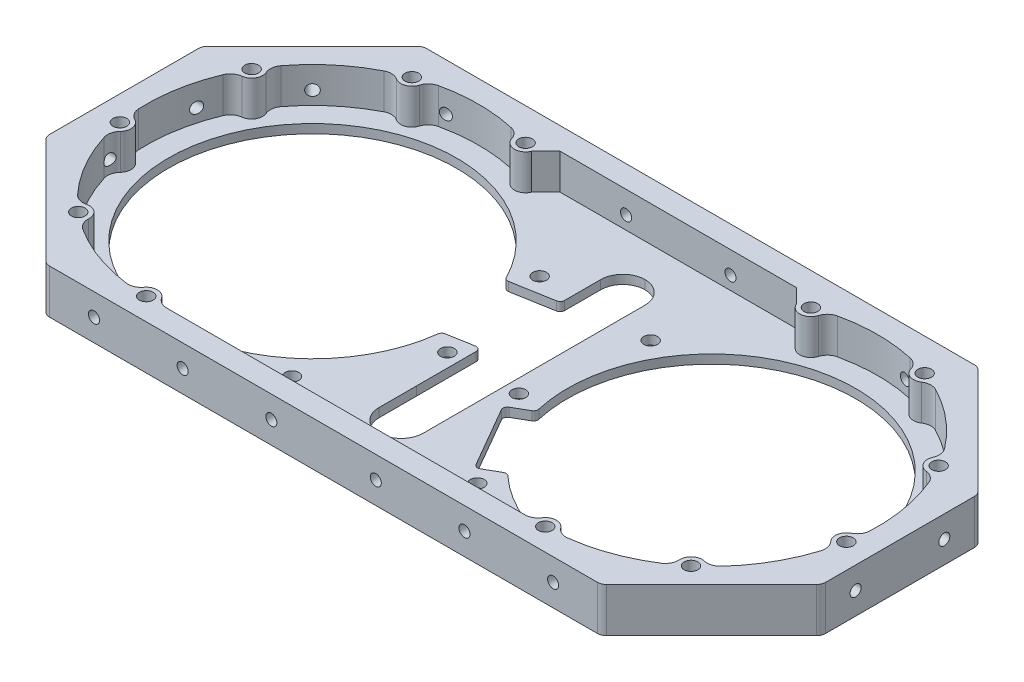
SolidWorks part; units mm, degrees
note: The reader was unsure of these and kept them because the rebuilt part matched: shared geometry of "草图2<8>".
ref_plane "前视基准面" through (0, 0, 0) normal (0, 0, 1) x (1, 0, 0)
ref_plane "上视基准面" through (0, 0, 0) normal (0, 1, 0) x (1, 0, 0)
ref_plane "右视基准面" through (0, 0, 0) normal (1, 0, 0) x (0, 0, -1)
sketch "草图2" plane through (0, 0, 0) normal (0, 1, 0) x (1, 0, 0)
  line L0 (0, 0) -> (90, 0) construction
  line L1 (16.5685, 40) -> (-16.5685, 40)
  line L2 (-16.5685, 40) -> (-40, 16.5685)
  line L3 (-40, 16.5685) -> (-40, -16.5685)
  line L4 (-40, -16.5685) -> (-16.5685, -40)
  line L5 (-16.5685, -40) -> (16.5685, -40)
  line L6 (16.5685, -40) -> (45, -11.5685)
  line L8 (45, 11.5685) -> (16.5685, 40)
  line L10 (16.5685, 40) -> (73.4315, 40)
  line L11 (130, 16.5685) -> (106.5685, 40)
  line L12 (106.5685, 40) -> (73.4315, 40)
  line L13 (73.4315, 40) -> (45, 11.5685)
  line L15 (45, -11.5685) -> (73.4315, -40)
  line L16 (73.4315, -40) -> (106.5685, -40)
  line L17 (106.5685, -40) -> (130, -16.5685)
  line L18 (130, -16.5685) -> (130, 16.5685)
  line L19 (40, -15.5147) -> (40, 0) [skipped]
  line L20 (50, -14.3614) -> (50, -29.8761) [skipped]
  line L21 (16.5685, -40) -> (73.4315, -40)
  line L22 (45, 11.5685) -> (45, -11.5685)
  line L23 (16.5685, 42.5) -> (-17.6041, 42.5)
  line L26 (57.524, 18.75) -> (57.2549, 17.2235)
  line L27 (53.0697, -6.5118) -> (53.8447, -7.8541)
  line L33 (58.7114, 19.7463) -> (57.524, 18.75)
  line L34 (53.3389, -4.9854) -> (53.0697, -6.5118)
  line L35 (-17.6041, 42.5) -> (-42.5, 17.6041)
  line L36 (-42.5, 17.6041) -> (-42.5, -17.6041)
  line L37 (-42.5, -17.6041) -> (-17.6041, -42.5)
  line L38 (-17.6041, -42.5) -> (16.5685, -42.5)
  line L39 (16.5685, -42.5) -> (73.4315, -42.5)
  line L40 (77.1742, 35.2385) -> (75.9869, 34.2422) [skipped]
  line L41 (102.8258, 35.2385) -> (101.2758, 35.2385) [skipped]
  line L42 (122.476, 18.75) -> (121.2886, 19.7463) [skipped]
  line L43 (126.9303, -6.5118) -> (126.6611, -4.9854) [skipped]
  line L44 (114.1045, -28.7267) -> (114.8795, -27.3843) [skipped]
  line L45 (90, -37.5) -> (91.4565, -36.9699) [skipped]
  line L46 (65.8955, -28.7267) -> (67.352, -29.2568) [skipped]
  line L47 (73.4315, -42.5) -> (107.6041, -42.5)
  line L48 (107.6041, -42.5) -> (132.5, -17.6041)
  line L49 (132.5, -17.6041) -> (132.5, 17.6041)
  line L50 (132.5, 17.6041) -> (107.6041, 42.5)
  line L51 (107.6041, 42.5) -> (73.4315, 42.5)
  line L52 (16.5685, 42.5) -> (73.4315, 42.5)
  line L53 (15.1452, 34.3056) -> (18.7041, 37.8645)
  line L56 (40, -37.5) -> (50, -37.5)
  line L59 (50, -30) -> (40, -30)
  line L60 (90, -37.5) -> (0, -37.5)
  line L61 (18.7041, 37.8645) -> (20.8396, 40)
  line L62 (50, -30) -> (50, 30)
  line L63 (74.8548, 34.3056) -> (71.2959, 37.8645)
  line L64 (71.2959, 37.8645) -> (69.1604, 40)
  line L65 (50, 30) -> (40, 30)
  line L66 (40, -30) -> (40, 30)
  line L67 (50, -30) -> (40, 30) construction
  line L68 (50, 30) -> (40, -30) construction
  circle A0 centre (0, 0) radius 40 construction
  circle A1 centre (0, 0) radius 37.5
  circle A2 centre (0, -37.5) radius 1.55
  circle A3 centre (-24.1045, -28.7267) radius 1.55
  circle A4 centre (-36.9303, -6.5118) radius 1.55
  circle A5 centre (-32.476, 18.75) radius 1.55
  circle A6 centre (-12.8258, 35.2385) radius 1.55
  circle A7 centre (12.8258, 35.2385) radius 1.55
  circle A8 centre (32.476, 18.75) radius 1.55
  circle A9 centre (36.9303, -6.5118) radius 1.55
  circle A10 centre (24.1045, -28.7267) radius 1.55
  circle A11 centre (90, 0) radius 40 construction
  circle A12 centre (90, 0) radius 37.5
  circle A13 centre (77.1742, 35.2385) radius 1.55
  circle A14 centre (102.8258, 35.2385) radius 1.55
  circle A15 centre (122.476, 18.75) radius 1.55
  circle A16 centre (126.9303, -6.5118) radius 1.55
  circle A17 centre (114.1045, -28.7267) radius 1.55
  circle A18 centre (90, -37.5) radius 1.55
  circle A19 centre (65.8955, -28.7267) radius 1.55
  circle A20 centre (53.0697, -6.5118) radius 1.55
  circle A21 centre (57.524, 18.75) radius 1.55
  circle A22 centre (0, 0) radius 32.5
  circle A23 centre (90, 0) radius 32.5
  circle A24 centre (0, -37.5) radius 2.5
  circle A25 centre (24.1045, -28.7267) radius 2.5
  circle A26 centre (36.9303, -6.5118) radius 2.5
  circle A27 centre (-24.1045, -28.7267) radius 2.5
  circle A28 centre (-36.9303, -6.5118) radius 2.5
  circle A29 centre (-32.476, 18.75) radius 2.5
  circle A30 centre (-12.8258, 35.2385) radius 2.5
  circle A31 centre (12.8258, 35.2385) radius 2.5
  circle A32 centre (32.476, 18.75) radius 2.5
  circle A33 centre (90, -37.5) radius 2.5
  circle A34 centre (65.8955, -28.7267) radius 2.5
  circle A35 centre (53.0697, -6.5118) radius 2.5
  circle A36 centre (57.524, 18.75) radius 2.5
  circle A37 centre (77.1742, 35.2385) radius 2.5
  circle A38 centre (102.8258, 35.2385) radius 2.5
  circle A39 centre (122.476, 18.75) radius 2.5
  circle A40 centre (126.9303, -6.5118) radius 2.5
  circle A41 centre (114.1045, -28.7267) radius 2.5
  point P13 (0, -37.5)
  point P35 (0, 0)
  point P73 (90, 0)
  point P84 (45, 0)
  point P86 (45, 0)
  point P140 (90, 0)
  dimension "D1" = 80
  dimension "D2" = 75
  dimension "D3" = 3.1
  dimension "D6" = 80
  dimension "D7" = 75
  dimension "D8" = 3.1
  dimension "D11" = 65
  dimension "D12" = 65
  dimension "D16" = 5
  dimension "D5" = 90
  dimension "D10" = 2.5
  dimension "D13" = 10
  dimension "D14" = 60
  dimension "D15" = 0.95
  dimension "D4" = 9
  dimension "D9" = 9
  dimension "D17" = 9
extrude "凸台-拉伸3" add sketch "草图2" along normal blind 10
extrude "凸台-拉伸4" add sketch "草图2<8>" along normal blind 2
sketch "草图2<8>" plane through (0, 0, 0) normal (0, 1, 0) x (1, 0, 0) same geometry as "草图2"
sketch "草图3" plane through (0, 2, 0) normal (0, 1, 0) x (1, 0, 0)
  line L0 (34.0024, 19.0192) -> (38.4567, -6.2427)
  line L1 (34.697, 15.0799) -> (37.7622, -2.3034)
  line L2 (34.697, 15.0799) -> (26.8185, 13.6907)
  line L3 (37.7622, -2.3034) -> (29.8837, -3.6926)
  line L4 (26.8185, 13.6907) -> (29.8837, -3.6926)
  line L5 (51.7274, -7.2868) -> (64.5531, -29.5017)
  line L6 (53.7274, -10.7509) -> (62.5531, -26.0376)
  line L7 (53.7274, -10.7509) -> (60.6556, -6.7509)
  line L8 (62.5531, -26.0376) -> (69.4813, -22.0376)
  line L9 (60.6556, -6.7509) -> (69.4813, -22.0376)
  line L10 (34.697, 15.0799) -> (37.7622, -2.3034)
  line L11 (34.697, 15.0799) -> (42.5755, 16.4691)
  line L12 (37.7622, -2.3034) -> (45.6406, -0.9142)
  line L13 (42.5755, 16.4691) -> (45.6406, -0.9142)
  circle A0 centre (36.9303, -6.5118) radius 1.55 construction
  circle A1 centre (32.476, 18.75) radius 1.55 construction
  circle A2 centre (36.9303, -6.5118) radius 1.55
  circle A3 centre (32.476, 18.75) radius 1.55
  circle A4 centre (65.8955, -28.7267) radius 1.55 construction
  circle A5 centre (53.0697, -6.5118) radius 1.55 construction
  circle A6 centre (65.8955, -28.7267) radius 1.55
  circle A7 centre (53.0697, -6.5118) radius 1.55
  line M99 (40, -16.5685) -> (40, 30)
  dimension "D4" = 4
  dimension "D1" = 4
  dimension "D2" = 4
  dimension "D3" = 8
  dimension "D5" = 4
  dimension "D6" = 8
  dimension "D7" = 8
extrude "切除-拉伸1" cut sketch "草图3" against normal blind 12 contours L2 L4 L3 L0 | L9 L7 L5 L8 | L0 L12 L11 M99 | L13 L11 L12 M99
fillet "圆角4" radius 1 8 edges at (67.3247, 1, 23.2827) (58.499, 1, 7.996) (62.5531, 1, 26.0376) (53.7274, 1, 10.7509) (32.3361, 1, 3.2602) (29.2709, 1, -14.1232) (40, 1, 1.9088) (40, 1, -16.015)
sketch "草图4" plane through (0, 2, 0) normal (0, 1, 0) x (1, 0, 0)
  line L0 (0, 37.5) -> (90, 37.5)
  line L5 (2.5, -37.5) -> (87.5, -37.5)
  line L6 (2.5, -37.5) -> (87.5, -37.5)
  line L9 (74.8548, 34.3056) -> (69.1604, 40)
  line L10 (69.1604, 40) -> (20.8396, 40)
  line L11 (20.8396, 40) -> (15.1452, 34.3056)
  line L17 (74.8548, 34.3056) -> (69.1604, 40)
  line L18 (69.1604, 40) -> (20.8396, 40)
  line L19 (20.8396, 40) -> (15.1452, 34.3056)
  arc A27 (92.4986, -37.4167) -> (87.5, -37.5) centre (90, -37.5) ccw
  arc A28 (92.4986, -37.4167) -> (112.1369, -30.2689) centre (90, 0) ccw
  arc A29 (115.965, -27.0568) -> (112.1369, -30.2689) centre (114.1045, -28.7267) ccw
  arc A30 (115.965, -27.0568) -> (126.4143, -8.958) centre (90, 0) ccw
  arc A31 (127.2821, -4.0367) -> (126.4143, -8.958) centre (126.9303, -6.5118) ccw
  arc A32 (127.2821, -4.0367) -> (123.6531, 16.5445) centre (90, 0) ccw
  arc A33 (121.1545, 20.8722) -> (123.6531, 16.5445) centre (122.476, 18.75) ccw
  arc A34 (121.1545, 20.8722) -> (105.1452, 34.3056) centre (90, 0) ccw
  arc A35 (100.4493, 36.0147) -> (105.1452, 34.3056) centre (102.8258, 35.2385) ccw
  arc A36 (100.4493, 36.0147) -> (79.5507, 36.0147) centre (90, 0) ccw
  arc A37 (74.8548, 34.3056) -> (79.5507, 36.0147) centre (77.1742, 35.2385) ccw
  arc A38 (10.4493, 36.0147) -> (15.1452, 34.3056) centre (12.8258, 35.2385) ccw
  arc A39 (10.4493, 36.0147) -> (-10.4493, 36.0147) centre (0, 0) ccw
  arc A40 (-15.1452, 34.3056) -> (-10.4493, 36.0147) centre (-12.8258, 35.2385) ccw
  arc A41 (-15.1452, 34.3056) -> (-31.1545, 20.8722) centre (0, 0) ccw
  arc A42 (-33.6531, 16.5445) -> (-31.1545, 20.8722) centre (-32.476, 18.75) ccw
  arc A43 (-33.6531, 16.5445) -> (-37.2821, -4.0367) centre (0, 0) ccw
  arc A44 (-36.4143, -8.958) -> (-37.2821, -4.0367) centre (-36.9303, -6.5118) ccw
  arc A45 (-36.4143, -8.958) -> (-25.965, -27.0568) centre (0, 0) ccw
  arc A46 (-22.1369, -30.2689) -> (-25.965, -27.0568) centre (-24.1045, -28.7267) ccw
  arc A47 (-22.1369, -30.2689) -> (-2.4986, -37.4167) centre (0, 0) ccw
  arc A48 (2.5, -37.5) -> (-2.4986, -37.4167) centre (0, -37.5) ccw
  arc A53 (92.4986, -37.4167) -> (87.5, -37.5) centre (90, -37.5) ccw
  arc A54 (92.4986, -37.4167) -> (112.1369, -30.2689) centre (90, 0) ccw
  arc A55 (115.965, -27.0568) -> (112.1369, -30.2689) centre (114.1045, -28.7267) ccw
  arc A56 (115.965, -27.0568) -> (126.4143, -8.958) centre (90, 0) ccw
  arc A57 (127.2821, -4.0367) -> (126.4143, -8.958) centre (126.9303, -6.5118) ccw
  arc A58 (127.2821, -4.0367) -> (123.6531, 16.5445) centre (90, 0) ccw
  arc A59 (121.1545, 20.8722) -> (123.6531, 16.5445) centre (122.476, 18.75) ccw
  arc A60 (121.1545, 20.8722) -> (105.1452, 34.3056) centre (90, 0) ccw
  arc A61 (100.4493, 36.0147) -> (105.1452, 34.3056) centre (102.8258, 35.2385) ccw
  arc A62 (100.4493, 36.0147) -> (79.5507, 36.0147) centre (90, 0) ccw
  arc A63 (74.8548, 34.3056) -> (79.5507, 36.0147) centre (77.1742, 35.2385) ccw
  arc A64 (10.4493, 36.0147) -> (15.1452, 34.3056) centre (12.8258, 35.2385) ccw
  arc A65 (10.4493, 36.0147) -> (-10.4493, 36.0147) centre (0, 0) ccw
  arc A66 (-15.1452, 34.3056) -> (-10.4493, 36.0147) centre (-12.8258, 35.2385) ccw
  arc A67 (-15.1452, 34.3056) -> (-31.1545, 20.8722) centre (0, 0) ccw
  arc A68 (-33.6531, 16.5445) -> (-31.1545, 20.8722) centre (-32.476, 18.75) ccw
  arc A69 (-33.6531, 16.5445) -> (-37.2821, -4.0367) centre (0, 0) ccw
  arc A70 (-36.4143, -8.958) -> (-37.2821, -4.0367) centre (-36.9303, -6.5118) ccw
  arc A71 (-36.4143, -8.958) -> (-25.965, -27.0568) centre (0, 0) ccw
  arc A72 (-22.1369, -30.2689) -> (-25.965, -27.0568) centre (-24.1045, -28.7267) ccw
  arc A73 (-22.1369, -30.2689) -> (-2.4986, -37.4167) centre (0, 0) ccw
  arc A74 (2.5, -37.5) -> (-2.4986, -37.4167) centre (0, -37.5) ccw
  dimension "D1" = 0
extrude "凸台-拉伸5" add sketch "草图4" along normal blind 8 contours L18 L19 L0 L17
fillet "圆角5" radius 3 21 edges at (-2.4986, 6, 37.4167) (-22.1369, 6, 30.2689) (-25.965, 6, 27.0568) (-36.4143, 6, 8.958) (-37.2821, 6, 4.0367) (-33.6531, 6, -16.5445) (-31.1545, 6, -20.8722) (-15.1452, 6, -34.3056) (-10.4493, 6, -36.0147) (10.4493, 6, -36.0147) (92.4986, 6, 37.4167) (115.965, 6, 27.0568) (112.1369, 6, 30.2689) (127.2821, 6, 4.0367) (126.4143, 6, 8.958) (121.1545, 6, -20.8722) (123.6531, 6, -16.5445) (100.4493, 6, -36.0147) (105.1452, 6, -34.3056) (79.5507, 6, -36.0147) (2.5, 6, 37.5)
fillet "圆角6" radius 3 1 edges at (87.5, 6, 37.5)
fillet "圆角7" radius 2 8 edges at (107.6041, 5, -42.5) (132.5, 5, -17.6041) (132.5, 5, 17.6041) (107.6041, 5, 42.5) (-17.6041, 5, 42.5) (-42.5, 5, 17.6041) (-42.5, 5, -17.6041) (-17.6041, 5, -42.5)
sketch "草图5" plane through (0, 0, -42.5) normal (0, 0, -1) x (-1, 0, 0)
  line L0 (16.7756, 5) -> (-106.7756, 5) construction
  line L4 (16.7756, 10) -> (-106.7756, 10)
  line L5 (-106.7756, 10) -> (-106.7756, 0)
  line L6 (-106.7756, 0) -> (16.7756, 0)
  line L8 (16.7756, 10) -> (-106.7756, 10)
  line L10 (-106.7756, 0) -> (16.7756, 0)
  line L13 (-106.7756, 10) -> (-106.7756, 0)
  line L15 (16.7756, 0) -> (16.7756, 10)
  line L16 (16.7756, 0) -> (16.7756, 10)
  point P8 (6.7756, 5)
  point P9 (-13.2244, 5)
  point P10 (-33.2244, 5)
  point P11 (-96.7756, 5)
  point P12 (-76.7756, 5)
  point P13 (-56.7756, 5)
  dimension "D4" = 20
  dimension "D5" = 10
  dimension "D6" = 20
  dimension "D8" = 20
  dimension "D9" = 20
  dimension "D1" = 0
hole_wizard "M3 螺纹孔1" positions "草图6" profile "草图8" tap size "M3" standard "GB"
sketch "草图6" plane through (0, 0, -42.5) normal (0, 0, -1) x (-1, 0, 0)
  point P0 (-96.7756, 5)
  point P3 (-76.7756, 5)
  point P6 (-56.7756, 5)
  point P9 (-13.2244, 5)
  point P12 (6.7756, 5)
  point P15 (-33.2244, 5)
sketch "草图8" plane through (96.7756, 5, -42.5) normal (1, 0, 0) x (0, 1, 0)
  line L0 (0, 0) -> (0, 8.2511)
  line L1 (0, 8.2511) -> (1.25, 7.5)
  line L2 (1.25, 7.5) -> (1.25, 0)
  line L5 (1.25, 0) -> (0, 0)
  line L10 (0, 8.2511) -> (-1.25, 7.5) construction
  line L11 (0, -6.35) -> (0, 107.95) construction
  dimension "螺纹孔钻头直径" = 2.5
  dimension "螺纹孔钻头深度" = 7.5
  dimension "导头角度" = 118
cosmetic thread "孔螺蚊线1" parameters "D1"=6, "D2"=3
cosmetic thread "孔螺蚊线2" parameters "D1"=6, "D2"=3
cosmetic thread "孔螺蚊线3" parameters "D1"=6, "D2"=3
cosmetic thread "孔螺蚊线4" parameters "D1"=6, "D2"=3
cosmetic thread "孔螺蚊线5" parameters "D1"=6, "D2"=3
cosmetic thread "孔螺蚊线6" parameters "D1"=6, "D2"=3
sketch "草图9" plane through (0, 0, 42.5) normal (0, 0, 1) x (1, 0, 0)
  line L0 (-16.7756, 5) -> (106.7756, 5) construction
  line L1 (-16.7756, 5) -> (106.7756, 5) construction
  point P0 (96.7756, 5)
  point P2 (76.7756, 5)
  point P4 (56.7756, 5)
  point P6 (33.2244, 5)
  point P8 (13.2244, 5)
  point P10 (-6.7756, 5)
hole_wizard "M3 螺纹孔3" positions "3D草图3" profile "草图12" tap size "M3" standard "GB"
sketch3d "3D草图3"
  point P0 (-6.7756, 5, 42.5)
  point P3 (13.2244, 5, 42.5)
  point P6 (33.2244, 5, 42.5)
  point P9 (56.7756, 5, 42.5)
  point P12 (76.7756, 5, 42.5)
  point P15 (96.7756, 5, 42.5)
sketch "草图12" plane through (-6.7756, 5, 42.5) normal (1, 0, 0) x (0, -1, 0)
  line L0 (0, 0) -> (0, 9.2511)
  line L1 (0, 9.2511) -> (1.25, 8.5)
  line L2 (1.25, 8.5) -> (1.25, 0)
  line L5 (1.25, 0) -> (0, 0)
  line L10 (0, 9.2511) -> (-1.25, 8.5) construction
  line L11 (0, -6.35) -> (0, 107.95) construction
  dimension "螺纹孔钻头直径" = 2.5
  dimension "螺纹孔钻头深度" = 8.5
  dimension "导头角度" = 118
cosmetic thread "孔螺蚊线13" parameters "D1"=6, "D2"=3
cosmetic thread "孔螺蚊线14" parameters "D1"=5, "D2"=3
cosmetic thread "孔螺蚊线15" parameters "D1"=5, "D2"=3
cosmetic thread "孔螺蚊线16" parameters "D1"=5, "D2"=3
cosmetic thread "孔螺蚊线17" parameters "D1"=5, "D2"=3
cosmetic thread "孔螺蚊线18" parameters "D1"=6, "D2"=3
sketch "草图13" plane through (132.5, 0, 0) normal (1, 0, 0) x (0, 0, -1)
  line L0 (-16.7756, 5) -> (16.7756, 5) construction
  line L4 (-16.7756, 0) -> (16.7756, 0)
  line L5 (16.7756, 0) -> (16.7756, 10)
  line L6 (16.7756, 10) -> (-16.7756, 10)
  line L8 (-16.7756, 0) -> (16.7756, 0)
  line L10 (16.7756, 10) -> (-16.7756, 10)
  line L13 (16.7756, 0) -> (16.7756, 10)
  line L15 (-16.7756, 10) -> (-16.7756, 0)
  line L16 (-16.7756, 10) -> (-16.7756, 0)
  point P6 (0, 5)
  point P7 (10, 5)
  point P8 (-10, 5)
  dimension "D2" = 10
  dimension "D3" = 10
  dimension "D1" = 0
hole_wizard "M3 螺纹孔4" positions "3D草图4" profile "草图14" tap size "M3" standard "GB"
sketch3d "3D草图4"
  point P0 (132.5, 5, 10)
  point P3 (132.5, 5, -10)
sketch "草图14" plane through (132.5, 5, 10) normal (0, 1, 0) x (0, 0, -1)
  line L0 (0, 0) -> (0, 9.2511)
  line L1 (0, 9.2511) -> (1.25, 8.5)
  line L2 (1.25, 8.5) -> (1.25, 0)
  line L5 (1.25, 0) -> (0, 0)
  line L10 (0, 9.2511) -> (-1.25, 8.5) construction
  line L11 (0, -6.35) -> (0, 107.95) construction
  dimension "螺纹孔钻头直径" = 2.5
  dimension "螺纹孔钻头深度" = 8.5
  dimension "导头角度" = 118
cosmetic thread "孔螺蚊线19" parameters "D1"=6, "D2"=3
cosmetic thread "孔螺蚊线20" parameters "D1"=6, "D2"=3
sketch "草图15" plane through (-42.5, 0, 0) normal (-1, 0, 0) x (0, 0, 1)
  line L4 (-16.7756, 0) -> (16.7756, 0)
  line L5 (16.7756, 0) -> (16.7756, 10)
  line L6 (16.7756, 10) -> (-16.7756, 10)
  line L8 (-16.7756, 0) -> (16.7756, 0)
  line L10 (16.7756, 10) -> (-16.7756, 10)
  line L12 (16.7756, 0) -> (16.7756, 10)
  line L14 (-16.7756, 10) -> (-16.7756, 0)
  line L15 (-16.7756, 10) -> (-16.7756, 0)
  point P2 (10, 5)
  point P4 (-10, 5)
  dimension "D1" = 0
hole_wizard "M3 螺纹孔5" positions "3D草图5" profile "草图16" tap size "M3" standard "GB"
sketch3d "3D草图5"
  point P0 (-42.5, 5, -10)
  point P3 (-42.5, 5, 10)
sketch "草图16" plane through (-42.5, 5, -10) normal (0, 1, 0) x (0, 0, 1)
  line L0 (0, 0) -> (0, 9.2511)
  line L1 (0, 9.2511) -> (1.25, 8.5)
  line L2 (1.25, 8.5) -> (1.25, 0)
  line L5 (1.25, 0) -> (0, 0)
  line L10 (0, 9.2511) -> (-1.25, 8.5) construction
  line L11 (0, -6.35) -> (0, 107.95) construction
  dimension "螺纹孔钻头直径" = 2.5
  dimension "螺纹孔钻头深度" = 8.5
  dimension "导头角度" = 118
cosmetic thread "孔螺蚊线21" parameters "D1"=6, "D2"=3
cosmetic thread "孔螺蚊线22" parameters "D1"=6, "D2"=3
fillet "圆角8" radius 5 4 edges at (40, 1, 30) (50, 1, 30) (50, 1, -30) (40, 1, -30)
sketch "草图18" plane through (-30.052, 0, -30.052) normal (-0.7071, 0, -0.7071) x (-0.7071, 0, 0.7071)
  line L0 (-16.7756, 10) -> (16.7756, 0) construction
  line L1 (16.7756, 10) -> (-16.7756, 0) construction
  line L4 (-16.7756, 0) -> (16.7756, 0)
  line L5 (16.7756, 0) -> (16.7756, 10)
  line L6 (16.7756, 10) -> (-16.7756, 10)
  line L7 (16.7756, 0) -> (16.7756, 10)
  line L8 (-16.7756, 0) -> (16.7756, 0)
  line L10 (16.7756, 10) -> (-16.7756, 10)
  line L14 (-16.7756, 10) -> (-16.7756, 0)
  line L15 (-16.7756, 10) -> (-16.7756, 0)
  point P2 (0, 5)
  dimension "D1" = 0
hole_wizard "M3 螺纹孔7" positions "3D草图6" profile "草图19" tap size "M3" standard "GB"
sketch3d "3D草图6"
  point P0 (-30.052, 5, -30.052)
cosmetic thread "孔螺蚊线23" parameters "D1"=5.0208, "D2"=3
sketch "草图19" plane through (-30.052, 5, -30.052) normal (0, 1, 0) x (-0.7071, 0, 0.7071)
  line L0 (0, 0) -> (0, 9.2511)
  line L1 (0, 9.2511) -> (1.25, 8.5)
  line L2 (1.25, 8.5) -> (1.25, 0)
  line L5 (1.25, 0) -> (0, 0)
  line L10 (0, 9.2511) -> (-1.25, 8.5) construction
  line L11 (0, -6.35) -> (0, 107.95) construction
  dimension "螺纹孔钻头直径" = 2.5
  dimension "螺纹孔钻头深度" = 8.5
  dimension "导头角度" = 118
sketch "草图20" plane through (75.052, 0, -75.052) normal (0.7071, 0, -0.7071) x (-0.7071, 0, -0.7071)
  line L0 (-80.4153, 10) -> (-46.864, 0) construction
  line L1 (-46.864, 10) -> (-80.4153, 0) construction
  line L4 (-80.4153, 0) -> (-46.864, 0)
  line L5 (-46.864, 0) -> (-46.864, 10)
  line L6 (-46.864, 10) -> (-80.4153, 10)
  line L7 (-46.864, 0) -> (-46.864, 10)
  line L8 (-80.4153, 0) -> (-46.864, 0)
  line L10 (-46.864, 10) -> (-80.4153, 10)
  line L14 (-80.4153, 10) -> (-80.4153, 0)
  line L15 (-80.4153, 10) -> (-80.4153, 0)
  point P2 (-63.6396, 5)
  point P4 (-63.6396, 5)
  point P6 (-63.6396, 5)
  dimension "D1" = 0
hole_wizard "M3 螺纹孔8" positions "3D草图7" profile "草图21" tap size "M3" standard "GB"
sketch3d "3D草图7"
  point P0 (120.052, 5, -30.052)
sketch "草图21" plane through (120.052, 5, -30.052) normal (0, 1, 0) x (-0.7071, 0, -0.7071)
  line L0 (0, 0) -> (0, 9.2511)
  line L1 (0, 9.2511) -> (1.25, 8.5)
  line L2 (1.25, 8.5) -> (1.25, 0)
  line L5 (1.25, 0) -> (0, 0)
  line L10 (0, 9.2511) -> (-1.25, 8.5) construction
  line L11 (0, -6.35) -> (0, 107.95) construction
  dimension "螺纹孔钻头直径" = 2.5
  dimension "螺纹孔钻头深度" = 8.5
  dimension "导头角度" = 118
cosmetic thread "孔螺蚊线24" parameters "D1"=5.0208, "D2"=3
